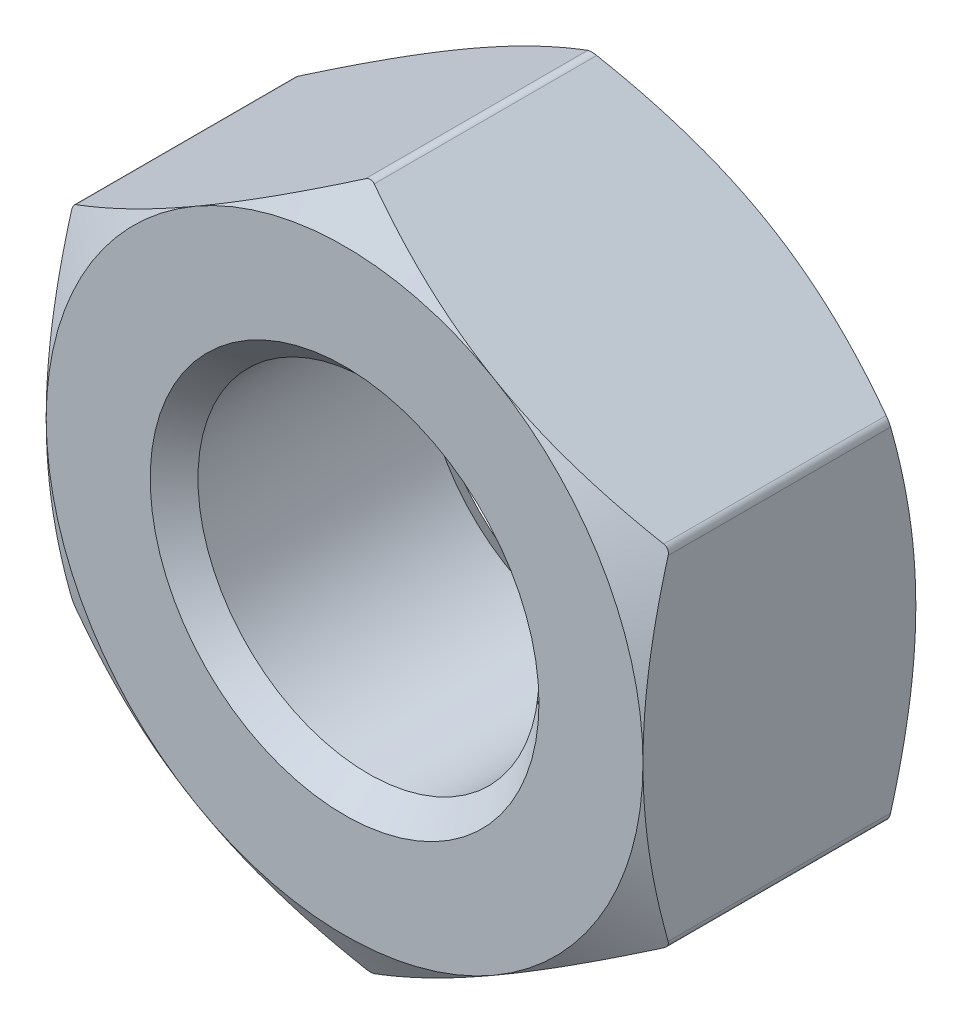
SolidWorks part; units mm, degrees
ref_plane "Front Plane" through (0, 0, 0) normal (0, 0, 1) x (1, 0, 0)
ref_plane "Top Plane" through (0, 0, 0) normal (0, 1, 0) x (1, 0, 0)
ref_plane "Right Plane" through (0, 0, 0) normal (1, 0, 0) x (0, 0, -1)
sketch "Sketch1" plane through (0, 0, 0) normal (0, 0, 1) x (1, 0, 0)
  line L1 (0, 4.0415) -> (-3.5, 2.0207)
  line L2 (-3.5, 2.0207) -> (-3.5, -2.0207)
  line L3 (-3.5, -2.0207) -> (0, -4.0415)
  line L4 (0, -4.0415) -> (3.5, -2.0207)
  line L5 (3.5, -2.0207) -> (3.5, 2.0207)
  line L6 (3.5, 2.0207) -> (0, 4.0415)
  circle A0 centre (0, 0) radius 3.5 construction
  dimension "Width" = 7
sketch "Sketch2" plane through (0, 0, 0) normal (1, 0, 0) x (0, 0, -1)
  line L0 (-1.6, 2) -> (1.6, 2) construction
  line L1 (-1.6, 4.0415) -> (1.6, 4.0415) construction
  line L2 (-1.6, 0) -> (1.6, 0) construction
  line L3 (0, 6.05) -> (0, -6.05) construction
  line L4 (1.5563, 2.0758) -> (2.2563, 2.0758) construction
  line L5 (2.2563, 2.0758) -> (1.9063, 1.4696) construction
  line L6 (1.9063, 1.4696) -> (1.5563, 2.0758) construction
  line L7 (1.6, 2) -> (2.2125, 2) construction
  line L8 (1.8625, 1.5453) -> (1.95, 1.5453) construction
  line L9 (1.9063, 1.5453) -> (1.9063, 1.4696) construction
  line L10 (1.9063, 2.0758) -> (1.9063, 2) construction
  line L11 (1.5781, 2.0379) -> (2.2344, 2.0379) construction
  line L12 (-1.6, 4.0415) -> (-1.6, 3.3852) construction
  line L13 (1.6, 4.0415) -> (1.6, 3.3852) construction
  point P7 (0, 2)
  point P23 (1.9063, 2.0379)
  dimension "Height" = 3.2
  dimension "Thread Size" = 4
  dimension "Thread Pitch" = 0.7
  dimension "Pitch/8" = 0.0875
sketch "Sketch3" plane through (0, 0, 0) normal (0, 0, 1) x (1, 0, 0)
  line L0 (3.5, -2.0207) -> (3.5, 2.0207) construction
  line L1 (0, 4.0415) -> (-3.5, 2.0207)
  line L2 (-3.5, 2.0207) -> (-3.5, -2.0207)
  line L3 (-3.5, -2.0207) -> (0, -4.0415)
  line L4 (0, -4.0415) -> (3.5, -2.0207)
  line L5 (3.5, -2.0207) -> (3.5, 2.0207)
  line L6 (3.5, 2.0207) -> (0, 4.0415)
  circle A0 centre (0, 0) radius 2
  circle A1 centre (0, 0) radius 3.5 construction
  circle A2 centre (0, 0) radius 3.5 construction
extrude "Boss-Extrude1" add sketch "Sketch3" along normal mid plane 3.2
sketch "Sketch4" plane through (0, 0, 1.6) normal (0, 0, 1) x (1, 0, 0)
  line L0 (0, 0) -> (0.9933, -1.1838) construction
  line L1 (0, 2.0758) -> (0, 1.4696) construction
  circle A0 centre (0, 0) radius 3.5
  circle A1 centre (0, 0) radius 3.5 construction
  circle A2 centre (0, 0) radius 1.5453 construction
  circle A3 centre (0, 0) radius 3.5 construction
  dimension "D2" = 40
extrude "Cut-Extrude1" cut sketch "Sketch4" against normal through all draft 60 flip side to cut
extrude "Cut-Extrude2" cut sketch "Sketch4<2>" along normal through all draft 60 from surface flip side to cut starting at face at (0, 0, -1.6)
sketch "Sketch4<2>" plane through (0, 0, 1.6) normal (0, 0, 1) x (1, 0, 0) same geometry as "Sketch4"
fillet "Fillet1" radius 0.105 6 edges at (3.5, -2.0207, 0) (0, -4.0415, 0) (-3.5, -2.0207, 0) (-3.5, 2.0207, 0) (0, 4.0415, 0) (3.5, 2.0207, 0)
chamfer "Chamfer1" distance 0.28 angle 45 2 edges at (2, 0, -1.6) (2, 0, 1.6)
equation "\"Pitch/8@Sketch2\" = \"Thread Pitch@Sketch2\" / 8"
equation "\"D1@Boss-Extrude1\" = \"Height@Sketch2\""
equation "\"D1@Fillet1\"=\"Width@Sketch1\" * .015"
equation "\"D1@Chamfer1\"=\"Thread Pitch@Sketch2\"*.4"
